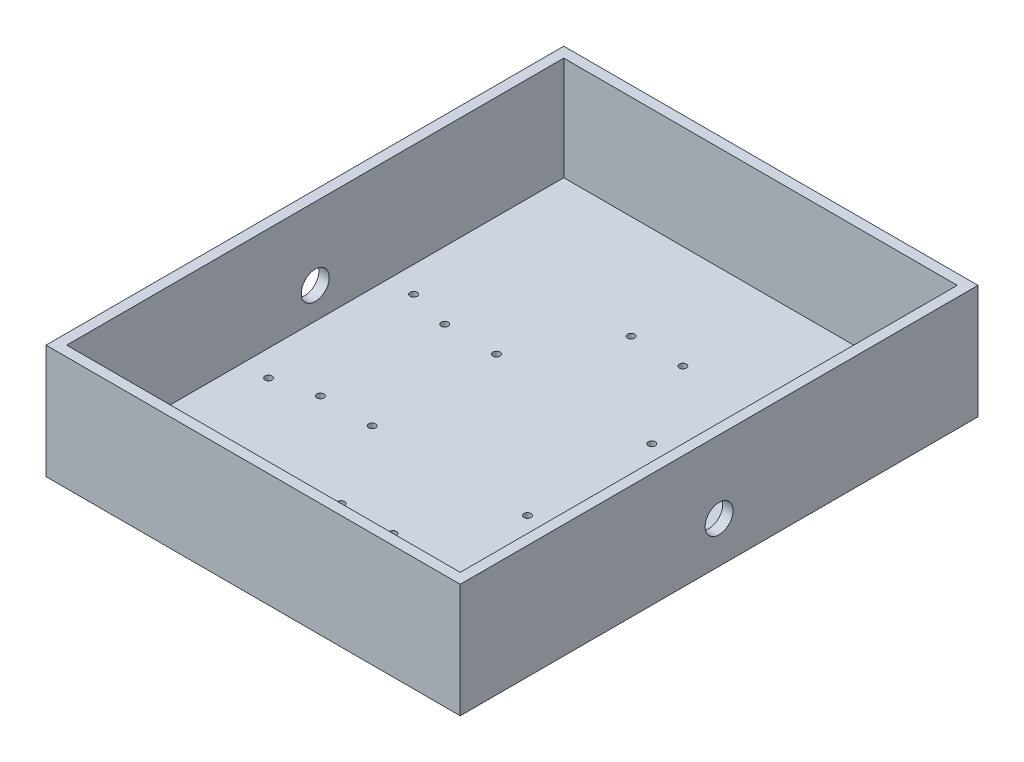
SolidWorks part; units mm, degrees
ref_plane "Front Plane" through (0, 0, 0) normal (0, 0, 1) x (1, 0, 0)
ref_plane "Top Plane" through (0, 0, 0) normal (0, 1, 0) x (1, 0, 0)
ref_plane "Right Plane" through (0, 0, 0) normal (1, 0, 0) x (0, 0, -1)
sketch "Sketch1" plane through (0, 0, 0) normal (0, 1, 0) x (1, 0, 0)
  line L0 (-95, 120) -> (95, 120)
  line L1 (95, 120) -> (95, -120)
  line L2 (95, -120) -> (-95, -120)
  line L3 (-95, -120) -> (-95, 120)
  line L4 (-95, 120) -> (95, 120)
  line L5 (-95, 120) -> (95, -120)
  point P7 (0, 0)
  dimension "D1" = 190
  dimension "D2" = 240
extrude "Boss-Extrude2" add sketch "Sketch1" along normal blind 50 contours L5 L3 L2 | L0 L5 L1 region at (-31.6667, 0, 40) region at (31.6667, 0, -40)
shell "Shell3" thickness 5 removed face at (0, 50, 0) outward yes
sketch "Sketch3" plane through (0, 0, 0) normal (0, 1, 0) x (1, 0, 0)
  line L2 (0, 16.5185) -> (0, -103.4815) construction
  line L3 (-117.9577, 0) -> (48.7807, 0) construction
  circle A12 centre (-12.5, 70) radius 1.7
  circle A13 centre (-37.5, 30) radius 1.7
  circle A14 centre (-62.5, 30) radius 1.7
  circle A15 centre (-82.5, 35) radius 1.7
  circle A16 centre (-12.5, -70) radius 1.7
  circle A17 centre (-37.5, -30) radius 1.7
  circle A18 centre (-62.5, -30) radius 1.7
  circle A19 centre (-82.5, -35) radius 1.7
  circle A20 centre (82.5, -35) radius 1.7
  circle A21 centre (62.5, -30) radius 1.7
  circle A22 centre (37.5, -30) radius 1.7
  circle A23 centre (12.5, -70) radius 1.7
  circle A24 centre (82.5, 35) radius 1.7
  circle A25 centre (62.5, 30) radius 1.7
  circle A26 centre (37.5, 30) radius 1.7
  circle A27 centre (12.5, 70) radius 1.7
  point P1 (0, 0)
  point P38 (62.5, 30)
  dimension "D8" = 3.4
  dimension "D1" = 25
  dimension "D2" = 20
  dimension "D3" = 5
  dimension "D4" = 40
  dimension "D5" = 12.5
  dimension "D6" = 25
  dimension "D7" = 30
extrude "Cut-Extrude1" cut sketch "Sketch3" along normal through all and the other way through all
sketch "Sketch5" plane through (0, 0, 0) normal (1, 0, 0) x (0, 0, -1)
  line L0 (125, -5) -> (-125, -5) construction
  circle A0 centre (0, 15) radius 6.75
  dimension "D2" = 13.5
  dimension "D1" = 20
extrude "Cut-Extrude2" cut sketch "Sketch5" against normal through all both and the other way through all
